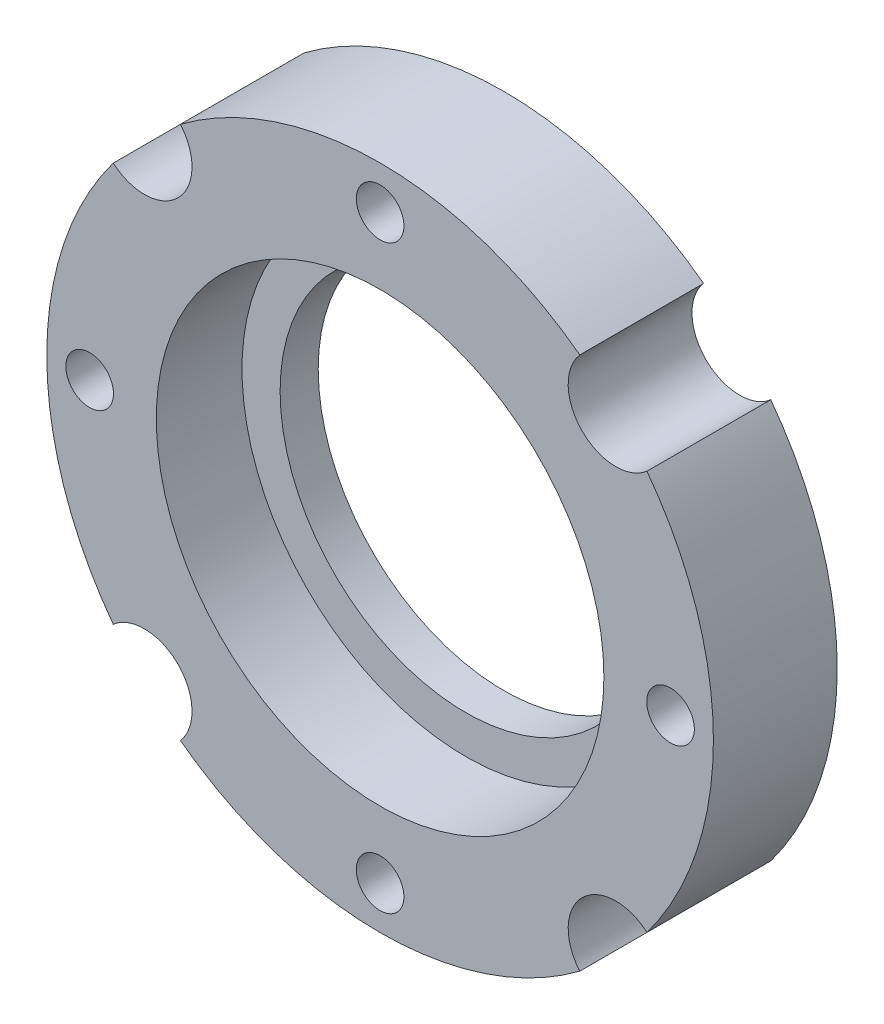
SolidWorks part; units mm, degrees
material "3.1325 (EN-AW 2017A)"
ref_plane "Płaszczyzna przednia" through (0, 0, 0) normal (0, 0, 1) x (1, 0, 0)
ref_plane "Płaszczyzna górna" through (0, 0, 0) normal (0, 1, 0) x (1, 0, 0)
ref_plane "Płaszczyzna prawa" through (0, 0, 0) normal (1, 0, 0) x (0, 0, -1)
sketch "Szkic1" plane through (0, 0, 0) normal (0, 0, 1) x (1, 0, 0)
  circle A0 centre (0, 0) radius 19.5
  circle A1 centre (0, 0) radius 35
  circle A2 centre (0, 0) radius 30.5
  point P5 (0, 30.5)
  point P6 (0, -30.5)
  dimension "D1" = 70
  dimension "D2" = 39
extrude "Dodanie-wyciągnięcie1" add sketch "Szkic1" along normal blind 13 contours A1 A2 | A2 A0 region at (-34.0101, 0, 0) region at (-29.6373, 0, 0)
sketch "Szkic2" plane through (0, 0, 13) normal (0, 0, 1) x (1, 0, 0)
  line L0 (0, 0) -> (21.2132, 21.2132)
  line L1 (0, 0) -> (35, 0)
  line L2 (0, 0) -> (21.2132, -21.2132)
  line L3 (0, 0) -> (-21.2132, -21.2132)
  arc A0 (-22.9566, 20.0809) -> (-22.9566, -20.0809) centre (0, 0) ccw
  circle A1 centre (0, 0) radius 35 construction
  circle A2 centre (24.7487, 24.7487) radius 5
  circle A3 centre (24.7487, -24.7487) radius 5
  circle A4 centre (-24.7487, -24.7487) radius 5
  circle A6 centre (-24.7487, 24.7487) radius 5
  arc A7 (20.0809, 22.9566) -> (-20.0809, 22.9566) centre (0, 0) ccw
  arc A8 (-20.0809, -22.9566) -> (20.0809, -22.9566) centre (0, 0) ccw
  arc A9 (22.9566, -20.0809) -> (22.9566, 20.0809) centre (0, 0) ccw
  point P3 (0, 30.5)
  point P4 (0, -30.5)
  circle M1 centre (0, 0) radius 35
  dimension "D1" = 45
  dimension "D2" = 10
  dimension "D3" = 10
  dimension "D4" = 10
  dimension "D5" = 10
hole_wizard "Otwory ustalające Ø5.0mm1" positions "Szkic3" profile "Szkic4" hole size "Ø5.0" standard "ISO" end condition through all
sketch "Szkic3" plane through (0, 0, 13) normal (0, 0, 1) x (1, 0, 0)
  circle A0 centre (0, 0) radius 30.5
  point P0 (0, 30.5)
  point P3 (0, -30.5)
  point P10 (-30.5, 0)
  point P12 (30.5, 0)
sketch "Szkic4" plane through (0, 30.5, 13) normal (1, 0, 0) x (0, -1, 0)
  line L0 (0, 0) -> (0, 13)
  line L1 (0, 13) -> (2.5, 13)
  line L2 (2.5, 13) -> (2.5, 0)
  line L5 (2.5, 0) -> (0, 0)
  line L11 (0, -6.35) -> (0, 107.95) construction
  dimension "Średnica otworu na wylot" = 5
  dimension "Głębokość otworu na wylot" = 13
sketch "Szkic6" plane through (0, 0, 13) normal (0, 0, 1) x (1, 0, 0)
  circle A0 centre (0, 0) radius 23.5
  circle A1 centre (0, 0) radius 19.5
  dimension "D1" = 47
  dimension "D2" = 39
extrude "Wytnij-wyciągnięcie1" cut sketch "Szkic6" against normal blind 9
extrude "Wytnij-wyciągnięcie2" cut sketch "Szkic2" against normal blind 14 contours A4 M1 | A4 M1 | A6 M1 | A6 M1 | A2 M1 | A2 M1 | A3 M1 | A3 M1 region at (23.2036, 23.2036, 13) region at (23.2036, -23.2036, 13) region at (-23.2036, -23.2036, 13) region at (26.2029, 26.2029, 13) region at (-23.2036, 23.2036, 13) region at (26.2029, -26.2029, 13) region at (-26.2029, -26.2029, 13) region at (-26.2029, 26.2029, 13)
